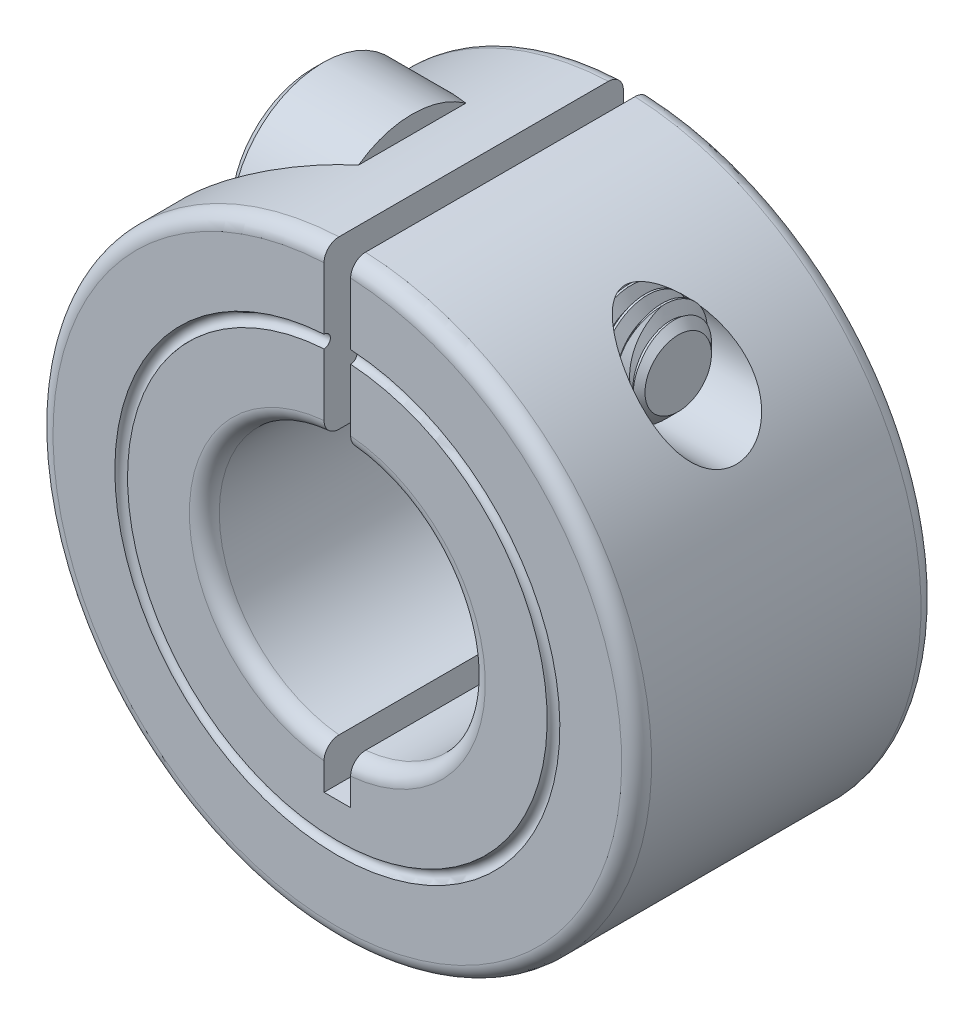
SolidWorks part; units mm, degrees
ref_plane "Front Plane" through (0, 0, 0) normal (0, 0, 1) x (1, 0, 0)
ref_plane "Top Plane" through (0, 0, 0) normal (0, 1, 0) x (1, 0, 0)
ref_plane "Right Plane" through (0, 0, 0) normal (1, 0, 0) x (0, 0, -1)
sketch "Sketch1" plane through (0, 0, 0) normal (0, 0, 1) x (1, 0, 0)
  line L0 (-0.4, 3.9799) -> (-0.4, 8.9911)
  line L2 (0.4, 3.9799) -> (0.4, 8.9911)
  line L3 (0, 0) -> (0, 3.9799) construction
  line L4 (0.4, 3.9799) -> (-0.4, 3.9799) construction
  line L5 (0, -9) -> (0, -4) construction
  line L6 (0, -4) -> (0, -6.5) construction
  line L7 (-0.4, -3.9799) -> (-0.4, -5.25)
  line L8 (-0.4, -5.25) -> (0.4, -5.25)
  line L9 (0.4, -3.9799) -> (0.4, -5.25)
  line L10 (-0.4, 6.4855) -> (0.4, 6.4855) construction
  circle A0 centre (0, 0) radius 9 construction
  circle A1 centre (0, 0) radius 4 construction
  arc A3 (-0.4, 8.9911) -> (0.4, 8.9911) centre (0, 0) ccw
  arc A4 (0.4, -3.9799) -> (0.4, 3.9799) centre (0, 0) ccw
  arc A5 (-0.4, 3.9799) -> (-0.4, -3.9799) centre (0, 0) ccw
  point P4 (9, 0)
  point P5 (-9, 0)
  point P19 (0, -5.25)
  dimension "Bore Dia" = 8
  dimension "OD" = 18
  dimension "Separation" = 0.8
extrude "Extrude1" add sketch "Sketch1" along normal mid plane 9
fillet "Fillet1" radius 0.45 6 edges at (0, -9, -4.5) (0, -9, 4.5) (-4, 0, -4.5) (-4, 0, 4.5) (4, 0, -4.5) (4, 0, 4.5)
sketch "Sketch2" plane through (0, 0, 0) normal (0, 1, 0) x (1, 0, 0)
  line L0 (0, 0) -> (-4, 0) construction
  line L1 (-4, 0) -> (-9, 0) construction
  line L2 (-6.5, 4.5) -> (-6.5, -4.5) construction
  line L3 (8.55, 4.5) -> (-8.55, 4.5) construction
  line L4 (-8.55, -4.5) -> (8.55, -4.5) construction
  line L5 (-9, 4.05) -> (-9, -4.05) construction
  line L6 (-4, 4.05) -> (-4, -4.05) construction
  line L8 (-6.6905, -4.5) -> (-6.3095, -4.5)
  line L9 (0, 4.5) -> (0, -4.5) construction
  line L10 (-0.4, 4.5) -> (-4.45, 4.5) construction
  arc A1 (-6.3095, -4.5) -> (-6.6905, -4.5) centre (-6.5, -4.5) ccw
  point P1 (-6.5, 0)
  dimension "D2" = 0.1905
revolve "Cut-Revolve1" cut sketch "Sketch2" angle 360 about L9
sketch "Sketch3" plane through (0, 0, 0) normal (0, 0, 1) x (1, 0, 0)
  line L0 (9, 6.4855) -> (-9, 6.4855)
  line L1 (-9, 6.4855) -> (-9, 3.733)
  line L2 (-9, 3.733) -> (-2.25, 3.733)
  line L4 (-2.25, 3.733) -> (-2.25, 4.9855)
  line L7 (-2.25, 4.9855) -> (9, 4.9855)
  line L8 (9, 4.9855) -> (9, 6.4855)
  line L9 (-9, 6.4855) -> (-11.7525, 6.4855) construction
  line L10 (-0.4, 6.4855) -> (0.4, 6.4855) construction
  dimension "D2" = 2.25
  dimension "D4" = 5.505
  dimension "Screw Dia" = 3
revolve "Cut-Revolve2" cut sketch "Sketch3" angle 360 about L9
sketch "Sketch4" plane through (0, 0, 0) normal (0, 0, 1) x (1, 0, 0)
  line L0 (-5.25, 6.4855) -> (-5.25, 9.2355)
  line L2 (-5.25, 9.2355) -> (-2.25, 9.2355)
  line L3 (-2.25, 9.2355) -> (-2.25, 7.9855)
  line L4 (-2.25, 7.9855) -> (5.75, 7.9855)
  line L5 (-2.25, 3.733) -> (-2.25, 4.9855) construction
  line L6 (5.75, 7.9855) -> (5.75, 6.4855)
  line L7 (-2.25, 4.9855) -> (9, 4.9855) construction
  line L8 (5.75, 6.4855) -> (-5.25, 6.4855)
  line L9 (5.75, 7.9855) -> (5.75, 4.9855) construction
  line L10 (-5.25, 6.4855) -> (-8, 6.4855) construction
  line L11 (-9, 6.4855) -> (-11.7525, 6.4855) construction
  dimension "Head Ht" = 3
  dimension "Screw Lg" = 8
  dimension "Head Dia" = 5.5
revolve "Revolve1" add sketch "Sketch4" angle 360 about L8
sketch "Sketch5" plane through (-5.25, 0, 0) normal (-1, 0, 0) x (0, -1, 0)
  line L1 (-5.7638, -1.25) -> (-5.0422, 0)
  line L2 (-5.0422, 0) -> (-5.7638, 1.25)
  line L3 (-5.7638, 1.25) -> (-7.2072, 1.25)
  line L4 (-7.2072, 1.25) -> (-7.9289, 0)
  line L5 (-7.9289, 0) -> (-7.2072, -1.25)
  line L6 (-7.2072, -1.25) -> (-5.7638, -1.25)
  circle A0 centre (-6.4855, 0) radius 1.25 construction
  dimension "Hex" = 2.5
extrude "Cut-Extrude1" cut sketch "Sketch5" against normal blind 2.5
chamfer "Chamfer1" distance 0.3175 angle 45 1 edges at (-5.25, 9.2355, 0)
sketch "Sketch6" plane through (5.75, 0, 0) normal (1, 0, 0) x (0, 1, 0)
  circle A0 centre (6.4855, 0) radius 1.5 construction
  circle A1 centre (6.4855, 0) radius 1.5
  point P3 (7.9855, 0)
curve "Helix/Spiral1" pitch 0.5 height 8 turns 16 parameters "Height"=8, "Pitch"=0.5
sketch "Sketch7" plane through (0, 0, 0) normal (0, 0, 1) x (1, 0, 0)
  line L0 (5.9688, 7.6066) -> (5.7187, 8.0397) construction
  line L1 (5.7187, 8.0397) -> (6.2187, 8.0397) construction
  line L2 (6.2187, 8.0397) -> (5.9688, 7.6066) construction
  line L3 (5.75, 7.9855) -> (6.1875, 7.9855) construction
  line L4 (5.9375, 7.6608) -> (6, 7.6608)
  line L5 (5.9687, 8.0397) -> (5.9687, 7.9855) construction
  line L6 (5.9687, 7.6608) -> (5.9688, 7.6066) construction
  line L7 (5.9375, 7.6608) -> (5.7344, 8.0126)
  line L8 (5.7344, 8.0126) -> (6.2031, 8.0126)
  line L9 (6.2031, 8.0126) -> (6, 7.6608)
  point P10 (5.9687, 8.0126)
  dimension "D1" = 0.5
  dimension "D2" = 0.0625
chamfer "Chamfer2" distance 0.5 angle 45 1 edges at (5.75, 7.9855, 0)
sweep "Cut-Sweep1" cut profiles "Sketch7" path "Helix/Spiral1"
equation "\"D1@Sketch3\" = \"Screw Dia@Sketch3\""
equation "\"D1@Cut-Extrude1\" = \"Hex@Sketch5\""
equation "\"D1@Fillet1\" = \"Width@Extrude1\"*.05"
equation "\"D4@Sketch3\" = \"Head Dia@Sketch4\" + .005"
equation "\"Height@Helix/Spiral1\" = \"Screw Lg@Sketch4\""
equation "\"D1@Sketch7\" = \"Pitch@Helix/Spiral1\""
equation "\"D2@Sketch7\" = \"D1@Sketch7\"/8"
equation "\"D1@Chamfer2\" = \"Pitch@Helix/Spiral1\""
equation "\"Separation@Sketch1\" = \"Bore Dia@Sketch1\"/10"
equation "\"D2@Sketch3\" = \"Screw Dia@Sketch3\"*.750"
